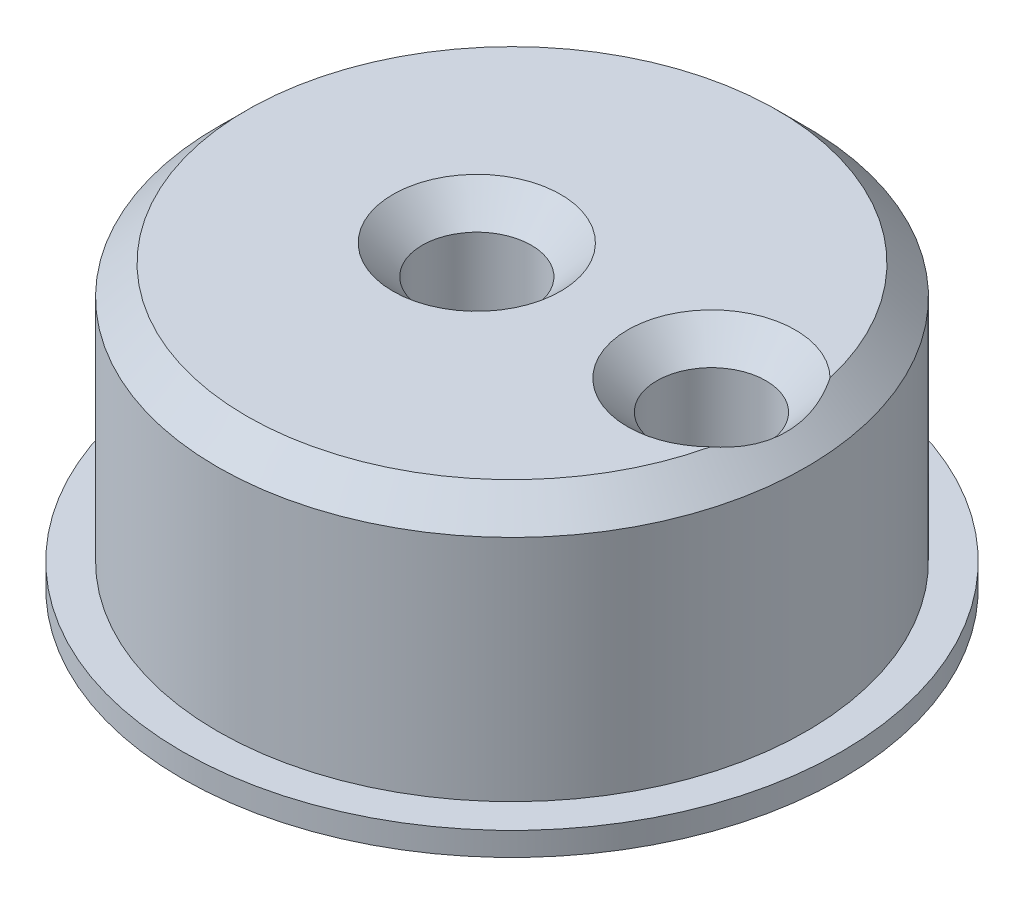
SolidWorks part; units mm, degrees
ref_plane "前视基准面" through (0, 0, 0) normal (0, 0, 1) x (1, 0, 0)
ref_plane "上视基准面" through (0, 0, 0) normal (0, 1, 0) x (1, 0, 0)
ref_plane "右视基准面" through (0, 0, 0) normal (1, 0, 0) x (0, 0, -1)
other "Configuration Table"
sketch "草图1" plane through (0, 0, 0) normal (0, 1, 0) x (1, 0, 0)
  line L0 (1.4, 6.4178) -> (1.4, -6.4114) construction
  line L1 (-5.7349, 0) -> (5.8104, 0) construction
  circle A0 centre (0, 0) radius 5.02
  circle A1 centre (3.4, 0) radius 0.93
  circle A2 centre (-0.6, 0) radius 0.93
  dimension "D1" = 10.04
  dimension "D3" = 4
  dimension "D4" = 1.86
  dimension "D2" = 1.4
extrude "凸台-拉伸1" add sketch "草图1" along normal blind 4.4
sketch "草图3" plane through (0, 0, 0) normal (0, -1, 0) x (1, 0, 0)
  circle A0 centre (3.4, 0) radius 0.93 construction
  circle A1 centre (0, 0) radius 5.02 construction
  circle A3 centre (-0.6, 0) radius 0.93 construction
  circle A4 centre (3.4, 0) radius 0.93
  circle A5 centre (-0.6, 0) radius 0.93
  circle A6 centre (0, 0) radius 5.02 construction
  circle A7 centre (0, 0) radius 5.62
  dimension "D1" = 0.6
extrude "凸台-拉伸2" add sketch "草图3" along normal blind 0.4
chamfer "倒角1" distance 0.5 angle 45 5 edges at (0, 4.4, 5.02) (-0.6, 4.4, -0.93) (3.4, 4.4, 0.93) (-0.6, -0.4, -0.93) (3.4, -0.4, -0.93)
ref_axis "基准轴1" through (0, 3.9, 0) along (0, -1, 0)
sketch "草图2" plane through (0, 0, 0) normal (0, 1, 0) x (1, 0, 0)
  line L0 (-5.9042, 0) -> (6.2358, 0) construction
